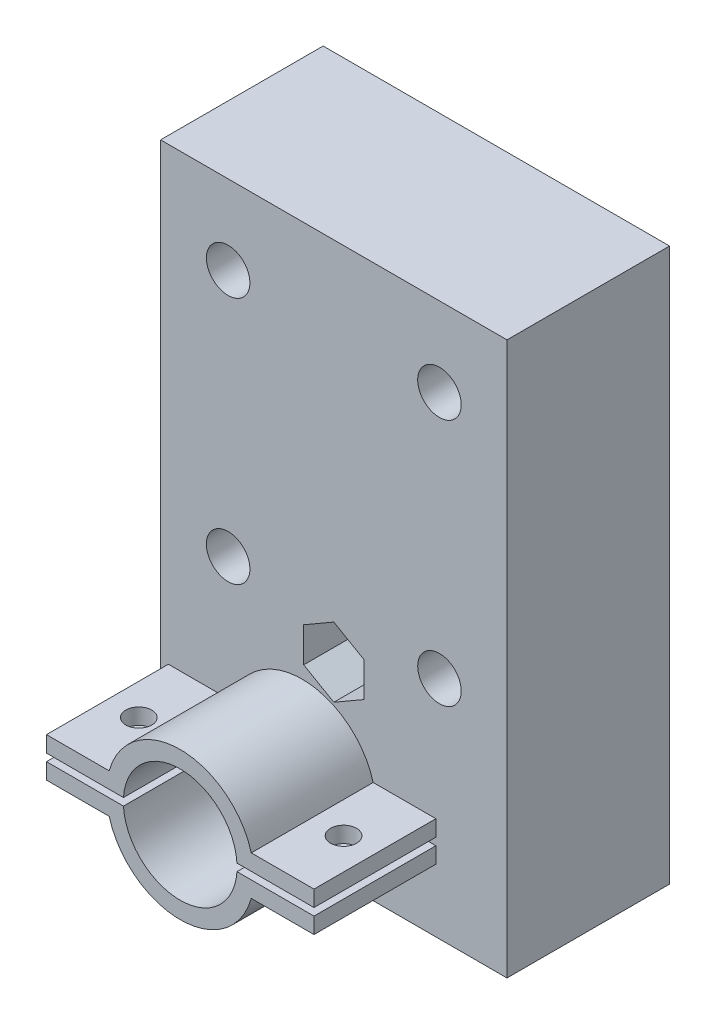
SolidWorks part; units mm, degrees
ref_plane "Front Plane" through (0, 0, 0) normal (0, 0, 1) x (1, 0, 0)
ref_plane "Top Plane" through (0, 0, 0) normal (0, 1, 0) x (1, 0, 0)
ref_plane "Right Plane" through (0, 0, 0) normal (1, 0, 0) x (0, 0, -1)
sketch "Sketch1" plane through (0, 0, 0) normal (0, 0, 1) x (1, 0, 0)
  line L0 (0, 25) -> (0, -25) construction
  line L1 (21.3115, 25) -> (-21.3115, 25)
  line L2 (21.3115, 25) -> (21.3115, -25)
  line L3 (21.3115, -25) -> (-21.3115, -25)
  line L4 (-21.3115, 25) -> (-21.3115, -25)
  line L5 (21.3115, 25) -> (-21.3115, -25) construction
  line L6 (21.3115, -25) -> (-21.3115, 25) construction
  line L7 (-21.3115, 0) -> (21.3115, 0) construction
  circle A0 centre (-13, -15.25) radius 2.677
  circle A1 centre (13, -15.25) radius 2.677
  circle A2 centre (13, 15.25) radius 2.677
  circle A3 centre (-13, 15.25) radius 2.677
  point P0 (0, 0)
  dimension "D1" = 30.5
  dimension "D2" = 26
  dimension "D3" = 50
extrude "Boss-Extrude1" add sketch "Sketch1" along normal blind 20
sketch "Sketch2" plane through (0, 0, 0) normal (0, 0, 1) x (1, 0, 0)
  circle A0 centre (0, 0) radius 8.73
  dimension "D1" = 17.46
extrude "Cut-Extrude2" cut sketch "Sketch2" along normal blind 7.94
sketch "Sketch3" plane through (0, 0, 0) normal (0, 0, -1) x (-1, 0, 0)
  circle A0 centre (0, -20) radius 2.2
  dimension "D1" = 4.4
  dimension "D2" = 20
extrude "Cut-Extrude3" cut sketch "Sketch3" against normal blind 10
sketch "Sketch5" plane through (0, 0, 0) normal (0, 0, -1) x (-1, 0, 0)
  line L1 (0, -15.7276) -> (-3.7, -17.8638)
  line L2 (-3.7, -17.8638) -> (-3.7, -22.1362)
  line L3 (-3.7, -22.1362) -> (0, -24.2724)
  line L4 (0, -24.2724) -> (3.7, -22.1362)
  line L5 (3.7, -22.1362) -> (3.7, -17.8638)
  line L6 (3.7, -17.8638) -> (0, -15.7276)
  circle A0 centre (0, -20) radius 3.7 construction
  dimension "D1" = 3.7
extrude "Cut-Extrude4" cut sketch "Sketch5" against normal through all from offset 7 offset against normal yes
sketch "Sketch6" plane through (0, 0, 0) normal (0, 0, -1) x (-1, 0, 0)
  circle A1 centre (3.8969, -32.824) radius 6.4
sketch "Sketch7" plane through (0, -25, 0) normal (0, -1, 0) x (1, 0, 0)
  line L1 (-21.3115, 20) -> (21.3115, 20)
  line L2 (-21.3115, 20) -> (-21.3115, 0)
  line L3 (-21.3115, 0) -> (21.3115, 0)
  line L4 (21.3115, 20) -> (21.3115, 0)
extrude "Boss-Extrude2" add sketch "Sketch7" along normal blind 18
extrude "Cut-Extrude5" cut sketch "Sketch6" against normal through all contours A1
sketch "Sketch8" plane through (0, 0, 20) normal (0, 0, 1) x (1, 0, 0)
  line L8 (3.0884, -32.3693) -> (10.2737, -32.3693)
  line L10 (-20.3552, -31.924) -> (-20.3552, -32.3693)
  line L12 (12.5615, -31.924) -> (12.5615, -32.3693)
  line L13 (10.2737, -32.3693) -> (12.5615, -32.3693)
  line L15 (-18.0674, -32.3693) -> (-10.8821, -32.3693)
  line L17 (-18.0674, -33.2788) -> (-10.8821, -33.2788)
  line L19 (12.5615, -33.2788) -> (10.2737, -33.2788)
  line L20 (12.5615, -33.2788) -> (12.5615, -33.724)
  line L23 (-18.0674, -32.3693) -> (-20.3552, -32.3693)
  line L25 (-20.3552, -33.2788) -> (-18.0674, -33.2788)
  line L26 (-20.3552, -33.2788) -> (-20.3552, -33.724)
  line L27 (3.0884, -33.2788) -> (10.2737, -33.2788)
  line L30 (-20.3552, -31.3876) -> (-20.3552, -32.3693)
  line L32 (12.5615, -31.3876) -> (12.5615, -32.3693)
  line L33 (-20.3552, -33.2788) -> (-20.3552, -34.2605)
  line L35 (12.5615, -33.2788) -> (12.5615, -34.2605)
  line L36 (-20.3552, -32.3693) -> (-20.3552, -30.3993)
  line L37 (-20.3552, -30.3993) -> (-12.6396, -30.3993)
  line L38 (-20.3552, -33.2788) -> (-20.3552, -35.2488)
  line L39 (-20.3552, -35.2488) -> (-12.6396, -35.2488)
  line L40 (12.5615, -32.3693) -> (12.5615, -30.3993)
  line L41 (12.5615, -30.3993) -> (4.8459, -30.3993)
  line L42 (12.5615, -33.2788) -> (12.5615, -35.2488)
  line L43 (12.5615, -35.2488) -> (4.8459, -35.2488)
  arc A0 (4.8459, -30.3993) -> (-12.6396, -30.3993) centre (-3.8969, -32.824) ccw
  arc A3 (-12.6396, -35.2488) -> (4.8459, -35.2488) centre (-3.8969, -32.824) ccw
  arc A7 (-12.6396, -35.2488) -> (5.0615, -34.2605) centre (-3.8969, -32.824) ccw
  arc A9 (4.8459, -30.3993) -> (-12.6396, -30.3993) centre (-3.8969, -32.824) ccw
  arc A13 (-10.8821, -33.2788) -> (3.0884, -33.2788) centre (-3.8969, -32.824) ccw
  arc A14 (3.0884, -32.3693) -> (-10.8821, -32.3693) centre (-3.8969, -32.824) ccw
  dimension "D2" = 1.8
extrude "Boss-Extrude5" add sketch "Sketch8" along normal blind 15 contours A9 A0 L10 A7 A3 L12 L27 L17 L15 L8 | A7 A3 L20 L19 L27 L17 L25 L26 region at (-3.8969, -25.4838, 20) region at (-14.4747, -33.6191, 20)
sketch "Sketch10" plane through (0, -43, 0) normal (0, -1, 0) x (1, 0, 0)
  line L0 (21.3115, 20) -> (-21.3115, 20) construction
  line L1 (-20.3552, 35) -> (-20.3552, 20) construction
  line L4 (12.5615, 35) -> (12.5615, 20) construction
  circle A0 centre (-16.4952, 27.5) radius 1.6
  circle A1 centre (8.7015, 27.5) radius 1.6
  dimension "D1" = 7.5
  dimension "D3" = 3.86
  dimension "D2" = 3.86
extrude "Cut-Extrude8" cut sketch "Sketch10" against normal through all
sketch "Sketch11" plane through (0, 0, 20) normal (0, 0, 1) x (1, 0, 0)
  circle A0 centre (-3.8969, -32.824) radius 7
extrude "Cut-Extrude9" cut sketch "Sketch11" against normal through all
